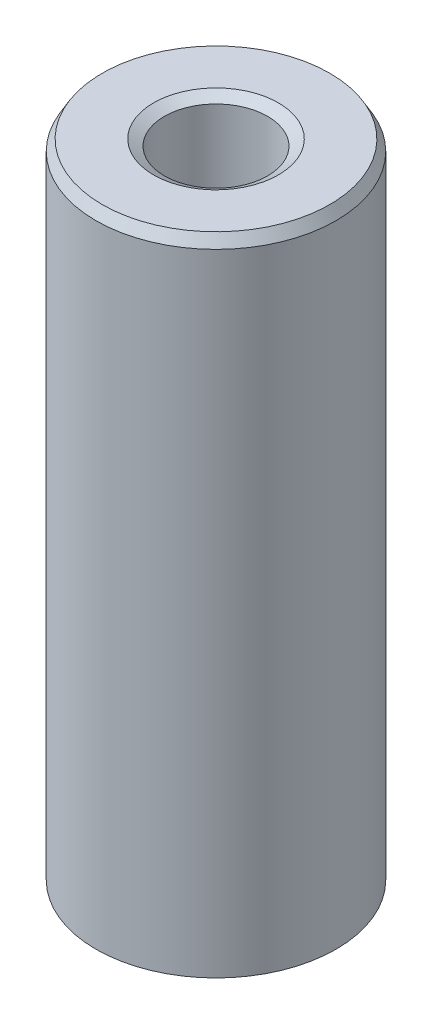
SolidWorks part; units mm, degrees
ref_plane "Front Plane" through (0, 0, 0) normal (0, 0, 1) x (1, 0, 0)
ref_plane "Top Plane" through (0, 0, 0) normal (0, 1, 0) x (1, 0, 0)
ref_plane "Right Plane" through (0, 0, 0) normal (1, 0, 0) x (0, 0, -1)
sketch "Sketch1" plane through (0, 0, 0) normal (0, 1, 0) x (1, 0, 0)
  circle A0 centre (0, 0) radius 35
  dimension "SLEEVE_OD" = 70
extrude "Boss-Extrude1" add sketch "Sketch1" along normal blind 188.9463
sketch "Sketch2" plane through (0, 0, 0) normal (0, 1, 0) x (1, 0, 0)
  circle A0 centre (0, 0) radius 15.0481
  dimension "BORE_D" = 30.0962
extrude "Cut-Extrude1" cut sketch "Sketch2" along normal through all
chamfer "Chamfer1" distance 3.1585 angle 30 4 edges at (0, 188.9463, 15.0481) (0, 0, 15.0481) (0, 0, 35) (0, 188.9463, 35) first distance on face at (0, 188.9463, 15.0481) first distance on face at (0, 0, 15.0481) first distance on face at (0, 188.9463, 35)
